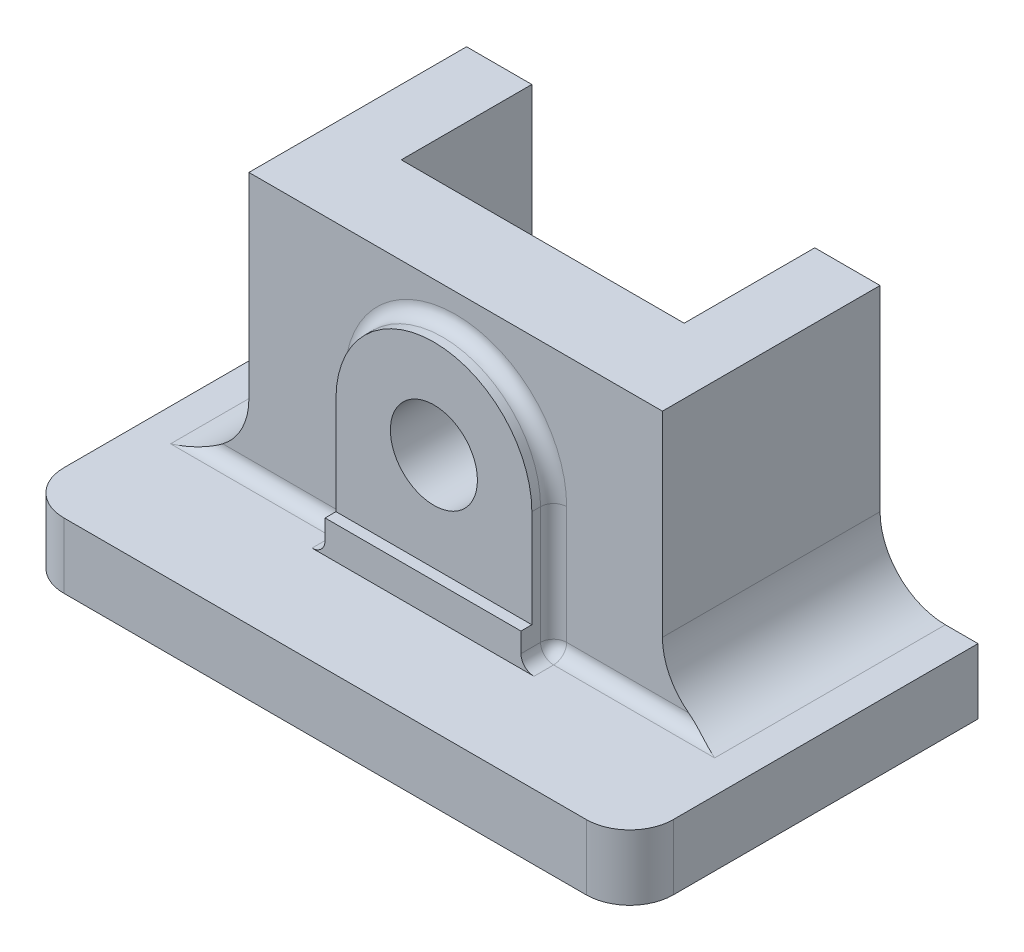
SolidWorks part; units mm, degrees
ref_plane "Front Plane" through (0, 0, 0) normal (0, 0, 1) x (1, 0, 0)
ref_plane "Top Plane" through (0, 0, 0) normal (0, 1, 0) x (1, 0, 0)
ref_plane "Right Plane" through (0, 0, 0) normal (1, 0, 0) x (0, 0, -1)
sketch "Sketch1" plane through (0, 0, 0) normal (0, 1, 0) x (1, 0, 0)
  line L1 (-38.1, -25.4) -> (38.1, -25.4)
  line L2 (-44.45, -19.05) -> (-44.45, 25.4)
  line L3 (-44.45, 25.4) -> (44.45, 25.4)
  line L4 (44.45, -19.05) -> (44.45, 25.4)
  line L5 (-44.45, -25.4) -> (44.45, 25.4) construction
  line L6 (-44.45, 25.4) -> (44.45, -25.4) construction
  arc A0 (38.1, -25.4) -> (44.45, -19.05) centre (38.1, -19.05) ccw
  arc A1 (-38.1, -25.4) -> (-44.45, -19.05) centre (-38.1, -19.05) cw
  point P0 (0, 0)
  dimension "D3" = 6.35
  dimension "D1" = 88.9
  dimension "D2" = 50.8
extrude "Boss-Extrude2" add sketch "Sketch1" along normal blind 9.525
sketch "Sketch4" plane through (0, 9.525, 0) normal (0, 1, 0) x (1, 0, 0)
  line L1 (44.45, 25.4) -> (-44.45, 25.4) construction
  line L2 (30.1625, 25.4) -> (30.1625, -6.35)
  line L3 (30.1625, -6.35) -> (-30.1625, -6.35)
  line L4 (-30.1625, -6.35) -> (-30.1625, 25.4)
  line L5 (-30.1625, 25.4) -> (-20.6375, 25.4)
  line L6 (-20.6375, 25.4) -> (-20.6375, 6.35)
  line L7 (-20.6375, 6.35) -> (20.6375, 6.35)
  line L8 (20.6375, 6.35) -> (20.6375, 25.4)
  line L9 (20.6375, 25.4) -> (30.1625, 25.4)
  point P5 (0, 25.4)
  point P10 (0, 0)
  point P12 (0, 0)
  point P13 (0, 0)
  point P14 (0, 0)
  point P15 (0, 0)
  point P16 (0, 0)
  point P17 (0, -6.35)
  point P18 (0, 0)
  dimension "D1" = 60.325
  dimension "D2" = 31.75
  dimension "D3" = 9.525
  dimension "D4" = 19.05
  dimension "D5" = 9.525
extrude "Boss-Extrude4" add sketch "Sketch4" along normal blind 38.1
sketch "Sketch5" plane through (0, 0, 6.35) normal (0, 0, 1) x (1, 0, 0)
  line L2 (-14.2875, 14.2875) -> (14.2875, 14.2875)
  line L5 (14.2875, 28.575) -> (14.2875, 14.2875)
  line L6 (-30.1625, 47.625) -> (30.1625, 47.625) construction
  line L8 (-14.2875, 28.575) -> (0, 28.575) construction
  line L9 (-14.2875, 14.2875) -> (-14.2875, 28.575)
  line L10 (-14.2875, 14.2875) -> (-14.2875, 28.575)
  line L11 (14.2875, 28.575) -> (14.2875, 14.2875)
  line L12 (14.2875, 14.2875) -> (-14.2875, 14.2875)
  line L13 (-30.1625, 9.525) -> (30.1625, 9.525) construction
  line L14 (-14.2875, 14.2875) -> (-14.2875, 9.525)
  line L15 (-14.2875, 9.525) -> (14.2875, 9.525)
  line L16 (14.2875, 9.525) -> (14.2875, 14.2875)
  arc A0 (14.2875, 28.575) -> (-14.2875, 28.575) centre (0, 28.575) ccw
  circle A1 centre (0, 28.575) radius 6.35
  line M9 (-30.1625, 9.525) -> (30.1625, 9.525)
  dimension "D1" = 19.05
  dimension "D2" = 28.575
  dimension "D3" = 4.7625
  dimension "D4" = 12.7
extrude "Boss-Extrude6" add sketch "Sketch5" along normal blind 3.175 contours L5 A0 L9 L2 region at (-13.8834, 21.4312, 6.35)
extrude "Boss-Extrude10" add sketch "Sketch5<6>" along normal blind 4.7625 contours L16 L2 L14 M9 region at (0, 11.9063, 6.35)
sketch "Sketch5<6>" plane through (0, 0, 6.35) normal (0, 0, 1) x (1, 0, 0) same geometry as "Sketch5"
extrude "Cut-Extrude1" cut sketch "Sketch5<7>" against normal through all contours A1 region at (0, 28.575, 6.35)
sketch "Sketch5<7>" plane through (0, 0, 6.35) normal (0, 0, 1) x (1, 0, 0) same geometry as "Sketch5"
fillet "Fillet1" radius 9.525 2 edges at (-30.1625, 9.525, -9.525) (30.1625, 9.525, -9.525)
fillet "Fillet4" radius 1.905 3 edges at (14.2875, 19.05, 6.35) (-14.2875, 19.05, 6.35) (0, 42.8625, 6.35)
fillet "Fillet5" radius 1.905 6 edges at (-14.2875, 9.525, 9.6837) (-14.8455, 9.525, 6.908) (14.2875, 9.525, 9.6837) (14.8455, 9.525, 6.908) (-27.94, 9.525, 6.35) (27.94, 9.525, 6.35)
